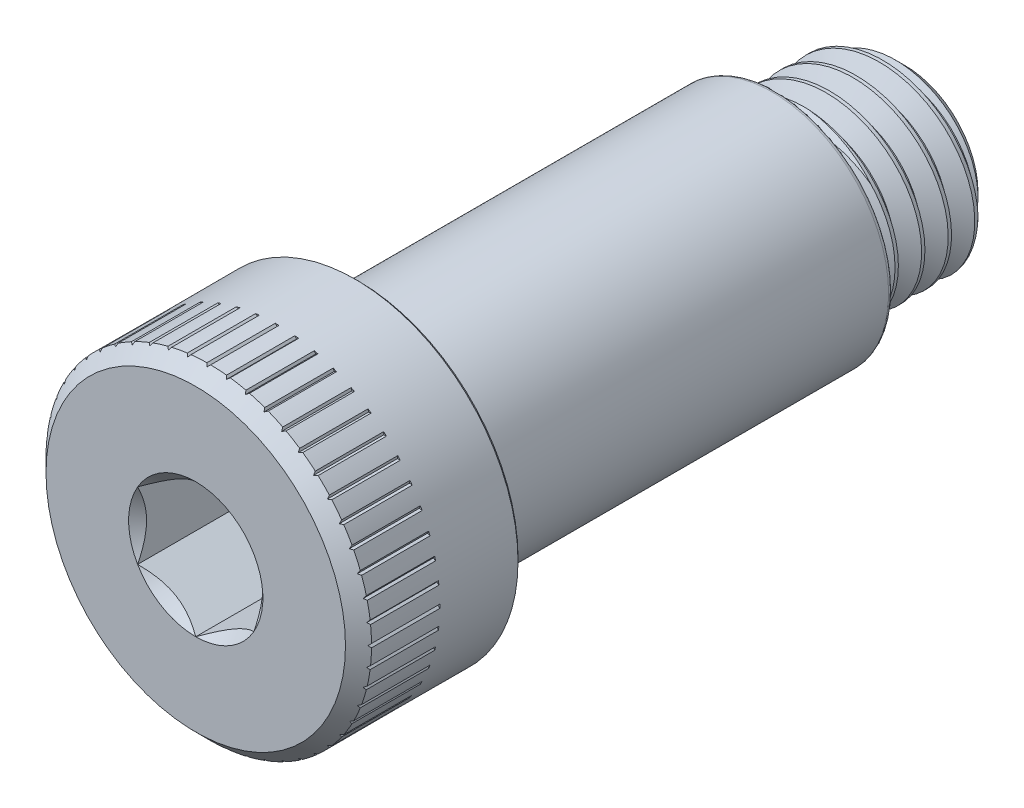
SolidWorks part; units mm, degrees
ref_plane "Front Plane" through (0, 0, 0) normal (0, 0, 1) x (1, 0, 0)
ref_plane "Top Plane" through (0, 0, 0) normal (0, 1, 0) x (1, 0, 0)
ref_plane "Right Plane" through (0, 0, 0) normal (1, 0, 0) x (0, 0, -1)
sketch "Sketch1" plane through (0, 0, 0) normal (1, 0, 0) x (0, 0, -1)
  line L0 (0, 0) -> (24.2094, 0) construction
  line L1 (0, 0) -> (0, 5.5562) construction
  line L2 (0, 5.5562) -> (5.5562, 5.5562) construction
  line L3 (5.5562, 5.5562) -> (5.5563, 3.9687) construction
  line L4 (5.5563, 3.9687) -> (19.8438, 3.9687) construction
  line L5 (19.8438, 3.9687) -> (19.8438, 2.8543) construction
  line L7 (24.2094, 3.175) -> (24.2094, 0) construction
  line L8 (24.2094, 0) -> (25.1165, 0) construction
  line L9 (24.2094, 3.175) -> (20.5954, 3.175) construction
  line L10 (20.5954, 3.175) -> (20.2746, 2.8543) construction
  line L11 (20.2746, 2.8543) -> (19.8438, 2.8543) construction
  point P4 (0, 1.9844)
  point P8 (21.9415, 3.175)
  point P10 (0, -1.9844)
  point P18 (21.9415, -3.175)
  dimension "Head Diameter" = 11.1125
  dimension "Head Height" = 5.5562
  dimension "Shoulder Length" = 14.2875
  dimension "Thread Size" = 6.35
  dimension "Drive Size" = 3.9688
  dimension "Pitch" = 0.9071
  dimension "D1" = 45
  dimension "D2" = 0.4536
  dimension "D3" = 0.4309
  dimension "Shoulder Diameter" = 7.9375
  dimension "Thread Length" = 4.3656
  dimension "D4" = 2.2679
sketch "Sketch2" plane through (0, 0, 0) normal (1, 0, 0) x (0, 0, -1)
  line L0 (24.2094, 3.175) -> (24.2094, 0) construction
  line L2 (5.5563, 3.9687) -> (19.8438, 3.9687) construction
  line L3 (0, 0) -> (24.2094, 0) construction
  line L4 (0, 0) -> (0, 5.5562) construction
  line L5 (0, 5.5562) -> (5.5562, 5.5562) construction
  line L6 (24.2094, 3.175) -> (24.2094, 0)
  line L8 (5.5563, 3.9687) -> (19.8438, 3.9687)
  line L9 (0, 0) -> (24.2094, 0)
  line L10 (0, 0) -> (0, 5.5562)
  line L11 (0, 5.5562) -> (5.5562, 5.5562)
  line L12 (19.8438, 3.9687) -> (19.8438, 2.8543) construction
  line L13 (5.5562, 5.5562) -> (5.5563, 3.9687) construction
  line L14 (19.8438, 3.9687) -> (19.8438, 2.8543)
  line L15 (5.5562, 5.5562) -> (5.5563, 3.9687)
  line L16 (20.2746, 2.8543) -> (19.8438, 2.8543) construction
  line L17 (20.5954, 3.175) -> (20.2746, 2.8543) construction
  line L18 (24.2094, 3.175) -> (20.5954, 3.175) construction
  line L19 (20.2746, 2.8543) -> (19.8438, 2.8543)
  line L20 (20.5954, 3.175) -> (20.2746, 2.8543)
  line L21 (24.2094, 3.175) -> (20.5954, 3.175)
revolve "Revolve1" add sketch "Sketch2" angle 360 about L9
sketch "Sketch3" plane through (0, 0, 0) normal (0, 0, 1) x (1, 0, 0)
  line L1 (1.9844, 1.1457) -> (0, 2.2914)
  line L2 (0, 2.2914) -> (-1.9844, 1.1457)
  line L3 (-1.9844, 1.1457) -> (-1.9844, -1.1457)
  line L4 (-1.9844, -1.1457) -> (0, -2.2914)
  line L5 (0, -2.2914) -> (1.9844, -1.1457)
  line L6 (1.9844, -1.1457) -> (1.9844, 1.1457)
  circle A0 centre (0, 0) radius 1.9844 construction
  dimension "D1" = 3.9688
extrude "Cut-Extrude1" cut sketch "Sketch3" against normal blind 3.3337
sketch "Sketch4" plane through (0, 0, 0) normal (0, 0, 1) x (1, 0, 0)
  circle A2 centre (0, 0) radius 2.2914
extrude "Cut-Extrude4" cut sketch "Sketch4" against normal through all draft 45
fillet "Fillet1" radius 0.3334 1 edges at (3.9687, 0, -5.5563)
chamfer "Chamfer1" distance 0.4445 angle 45 1 edges at (5.5562, 0, 0)
chamfer "Chamfer2" distance 0.6804 angle 45 1 edges at (3.175, 0, -24.2094)
chamfer "Chamfer3" distance 0.1111 angle 45 1 edges at (5.5562, 0, -5.5562)
fillet "Fillet2" radius 0.5556 1 edges at (2.8543, 0, -19.8438)
fillet "Fillet3" radius 0.1588 1 edges at (3.9687, 0, -19.8438)
ref_plane "Plane1" through (0, 0, -20.2746) normal (0, 0, 1) x (1, 0, 0)
split "Split1" trim tools "Plane1" bodies to split 107 resulting bodies 109 110
sketch "Sketch9" plane through (0, 0, 0) normal (0, 0, 1) x (1, 0, 0)
  circle A0 centre (0, 0) radius 5.5562 construction
  dimension "D1" = 11.1125
sketch "Sketch5" plane through (0, 0, -24.2094) normal (0, 0, -1) x (-1, 0, 0)
  circle A0 centre (0, 0) radius 3.175 construction
  circle A1 centre (0, 0) radius 3.175
curve "Helix/Spiral1" pitch 0.9071 height 5.2728 radius 3.175 centre (0, 0, -24.2094) axis (0, 0, 1) start towards (0, 1, 0)
sketch "Sketch6" plane through (0, 0, 0) normal (1, 0, 0) x (0, 0, -1)
  line L0 (24.2094, 3.175) -> (25.0031, 3.175)
  line L1 (25.0031, 3.175) -> (24.6629, 2.5858)
  line L2 (24.5496, 2.5858) -> (24.2094, 3.175)
  line L3 (24.6629, 2.5858) -> (24.5496, 2.5858)
  line L4 (24.6062, 2.5858) -> (24.6062, 3.175) construction
  line L5 (24.3795, 2.8804) -> (24.833, 2.8804) construction
  point P11 (24.6062, 2.8804)
  dimension "D1" = 60
  dimension "D2" = 0.1134
  dimension "D3" = 0.4536
sweep "Cut-Sweep1" cut profiles "Sketch6" path "Helix/Spiral1" align with end faces yes
sketch "Sketch7" plane through (0, 0, -20.2746) normal (0, 0, -1) x (-1, 0, 0)
  circle A0 centre (0, 0) radius 2.8543 construction
  circle A1 centre (0, 0) radius 2.8543
extrude "Boss-Extrude1" add sketch "Sketch7" along normal through all draft 45
combine bodies "Combine1" operation type add bodies to combine 109 111
sketch "Sketch8" plane through (0, 0, 0) normal (0, 0, 1) x (1, 0, 0)
  line L0 (0, 0) -> (0, 5.5562) construction
  line L1 (-0.0667, 5.5588) -> (0, 5.4921)
  line L2 (0, 5.4921) -> (0.0667, 5.5588)
  line L3 (0.0667, 5.5588) -> (-0.0667, 5.5588)
  circle A1 centre (0, 0) radius 5.5562 construction
  circle A2 centre (0, 0) radius 5.5562 construction
  dimension "D1" = 11.1125
  dimension "D2" = 0.1334
  dimension "D3" = 0.0025
extrude "Cut-Extrude5" cut sketch "Sketch8" against normal blind 2.7781
pattern_circular "CirPattern1" count 52 over 360 about axis through (0, 0, -0.4445) along (0, 0, -1) of "Cut-Extrude5"
equation "\"D1@Sketch3\"=\"Drive Size@Sketch1\""
equation "\"D1@Cut-Extrude1\"=\"Head Height@Sketch1\"*.6"
equation "\"D1@Fillet1\"=\"Head Diameter@Sketch1\"*.03"
equation "\"D1@Chamfer1\"=\"Head Diameter@Sketch1\"*.04"
equation "\"D1@Chamfer2\"=\"Pitch@Sketch1\"*.75"
equation "\"D1@Chamfer3\"=\"Head Diameter@Sketch1\"*.01"
equation "\"D2@Sketch1\"=\"Pitch@Sketch1\"*.5"
equation "\"D3@Sketch1\"=\"D2@Sketch1\"*.95"
equation "\"D1@Fillet2\"=\"Shoulder Diameter@Sketch1\"*.07"
equation "\"D1@Fillet3\"=\"Shoulder Diameter@Sketch1\"*.02"
equation "\"D3@Helix/Spiral1\"=\"Thread Length@Sketch1\"+\"Pitch@Sketch1\""
equation "\"D4@Helix/Spiral1\"=\"Pitch@Sketch1\""
equation "\"D2@Sketch6\"=\"Pitch@Sketch1\"*.125"
equation "\"D3@Sketch6\"=\"Pitch@Sketch1\"*.5"
equation "\"D1@Cut-Extrude5\"=\"Head Height@Sketch1\"*.5"
equation "\"D1@CirPattern1\"=((3.14*\"D1@Sketch8\")/\"D2@Sketch8\")*.2"
equation "\"D1@Sketch9\"=\"Head Diameter@Sketch1\""
equation "\"D4@Sketch1\"=\"Pitch@Sketch1\"*2.5"
equation "\"D2@Sketch8\"=\"D1@Sketch8\"*.012"
